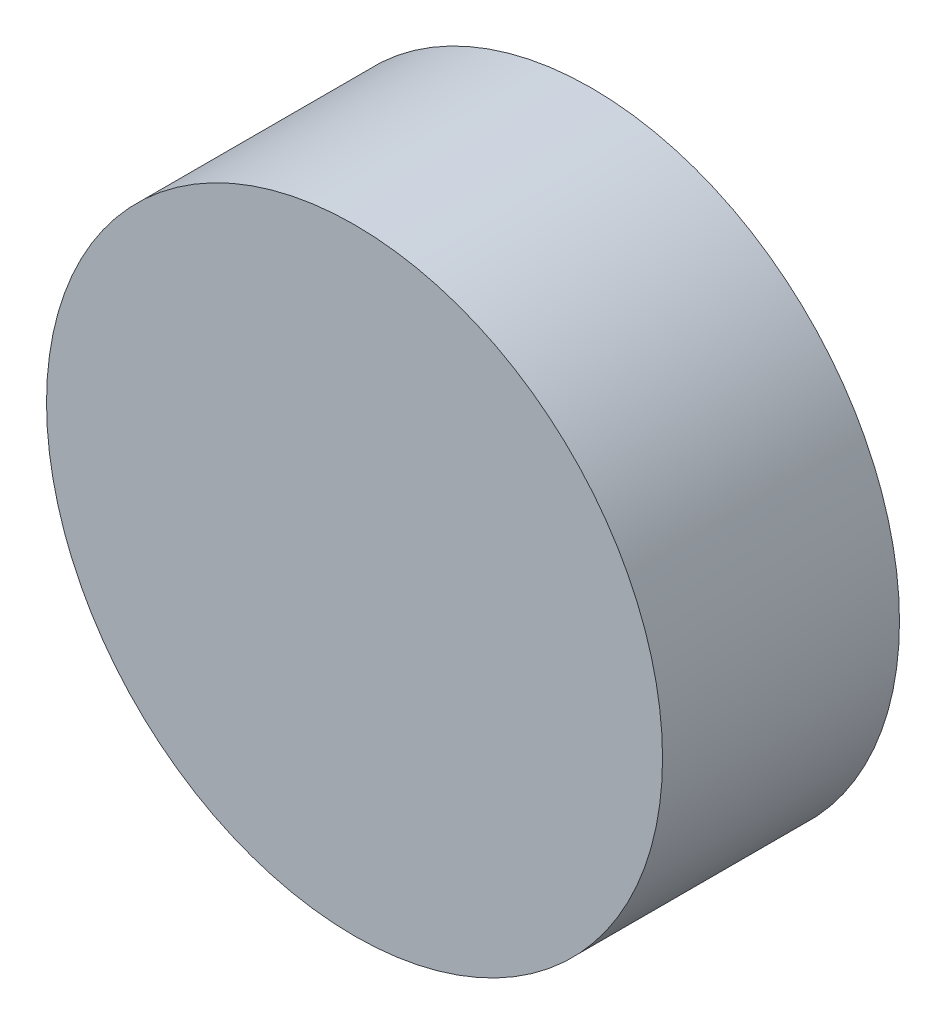
SolidWorks part; units mm, degrees
ref_plane "Спереди" through (0, 0, 0) normal (0, 0, 1) x (1, 0, 0)
ref_plane "Сверху" through (0, 0, 0) normal (0, 1, 0) x (1, 0, 0)
ref_plane "Справа" through (0, 0, 0) normal (1, 0, 0) x (0, 0, -1)
sketch "Эскиз1" plane through (0, 0, 0) normal (0, 0, 1) x (1, 0, 0)
  circle A0 centre (0, 0) radius 32.5
extrude "CS_LEFT_WHEEL" add sketch "Эскиз1" along normal blind 25
ref_axis "AXIS_LEFT_WHEEL" through (0, 0, 25) along (0, 0, -1)
